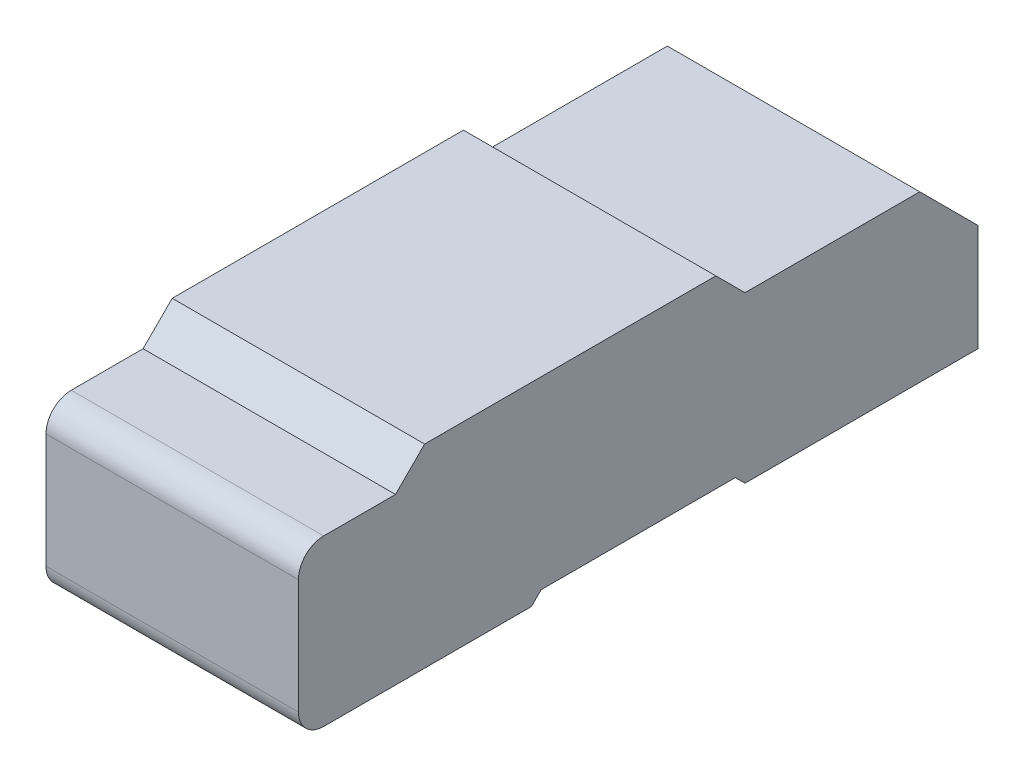
SolidWorks part; units mm, degrees
ref_plane "Front Plane" through (0, 0, 0) normal (0, 0, 1) x (1, 0, 0)
ref_plane "Top Plane" through (0, 0, 0) normal (0, 1, 0) x (1, 0, 0)
ref_plane "Right Plane" through (0, 0, 0) normal (1, 0, 0) x (0, 0, -1)
sketch "Sketch1" plane through (0, 0, 0) normal (0, 1, 0) x (1, 0, 0)
  line L1 (0, 0) -> (150, 0)
  line L2 (0, 0) -> (0, 350)
  line L3 (0, 350) -> (150, 350)
  line L4 (150, 0) -> (150, 350)
  dimension "D1" = 150
  dimension "D2" = 350
sketch "Sketch2" plane through (0, 0, 0) normal (1, 0, 0) x (0, 0, -1)
  line L0 (0, 0) -> (350, 0) construction
  line L1 (0, 0) -> (0, 85)
  line L2 (0, 85) -> (50, 85)
  line L3 (50, 85) -> (65, 100)
  line L4 (65, 100) -> (215, 100)
  line L5 (215, 100) -> (230, 85)
  line L6 (230, 85) -> (320, 85)
  line L7 (320, 85) -> (350, 55)
  line L8 (350, 55) -> (350, 0)
  line L9 (0, 0) -> (120, 0)
  line L10 (120, 0) -> (125, 5)
  line L11 (125, 5) -> (225, 5)
  line L12 (225, 5) -> (230, 0)
  line L13 (230, 0) -> (350, 0)
  dimension "D1" = 350
  dimension "D2" = 85
  dimension "D3" = 50
  dimension "D4" = 15
  dimension "D5" = 150
  dimension "D6" = 90
  dimension "D7" = 135
  dimension "D8" = 120
  dimension "D9" = 5
  dimension "D10" = 45
extrude "Boss-Extrude1" add sketch "Sketch2" along normal blind 130
fillet "Fillet1" radius 13 2 edges at (65, 0, 0) (65, 85, 0)
